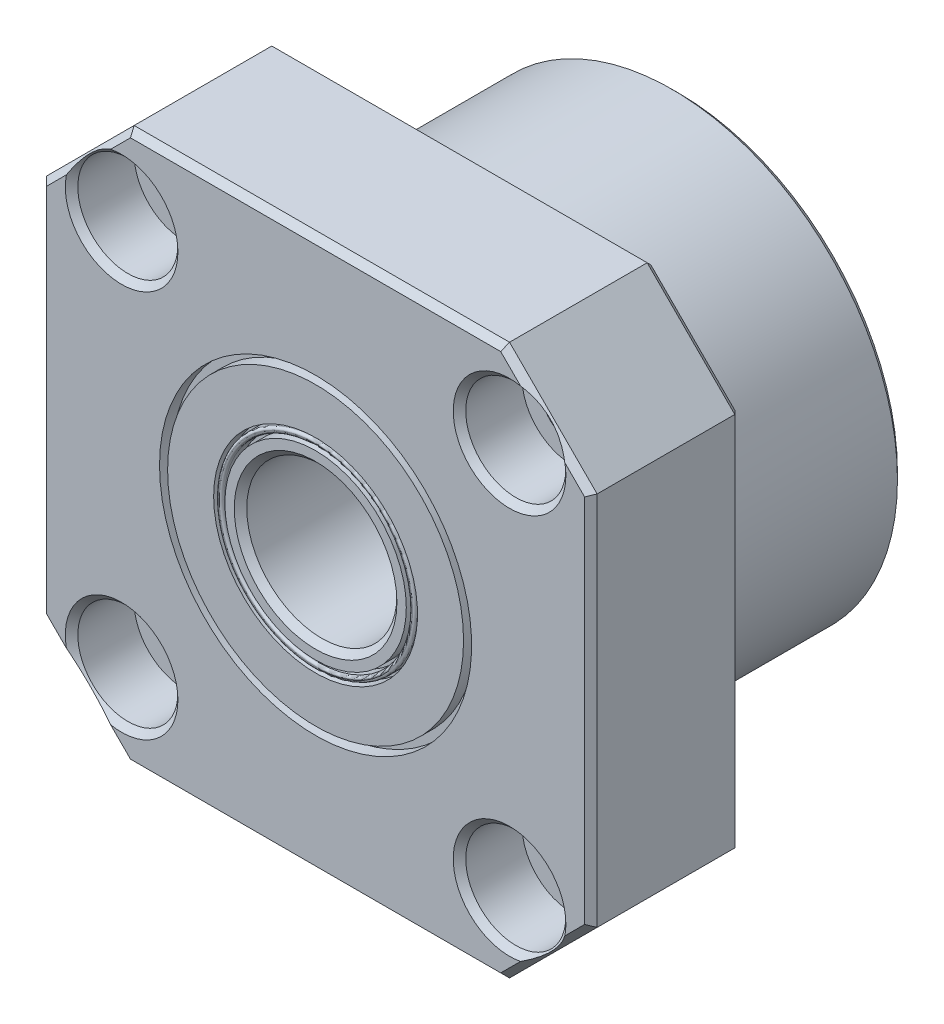
SolidWorks part; units mm, degrees
ref_plane "Plano frontal" through (0, 0, 0) normal (0, 0, 1) x (1, 0, 0)
ref_plane "Plano superior" through (0, 0, 0) normal (0, 1, 0) x (1, 0, 0)
ref_plane "Plano direito" through (0, 0, 0) normal (1, 0, 0) x (0, 0, -1)
sketch "Esboço1" plane through (0, 0, 0) normal (0, 0, 1) x (1, 0, 0)
  line L0 (0, 47.516) -> (0, -52.6832) construction
  line L1 (90.8564, 0) -> (-91.569, 0) construction
  line L3 (-22, 22) -> (22, 22)
  line L4 (-22, 22) -> (-22, -22)
  line L5 (-22, -22) -> (22, -22)
  line L6 (22, 22) -> (22, -22)
  point P9 (22, 0)
  point P10 (0, 22)
  dimension "D1" = 44
  dimension "D2" = 44
extrude "Ressalto-extrusão1" add sketch "Esboço1" along normal blind 12
sketch "Esboço2" plane through (0, 0, 0) normal (0, 0, -1) x (-1, 0, 0)
  line L0 (0, 33.6256) -> (0, -34.0961) construction
  line L1 (39.4463, 0) -> (-45.621, 0) construction
  circle A0 centre (0, 0) radius 18
  dimension "D1" = 36
extrude "Ressalto-extrusão2" add sketch "Esboço2" along normal blind 17
chamfer "Chanfro1" distance 7 angle 45 4 edges at (-22, -22, 6) (22, -22, 6) (22, 22, 6) (-22, 22, 6)
sketch "Esboço3" plane through (0, 0, 12) normal (0, 0, 1) x (1, 0, 0)
  line L0 (0, 30.9393) -> (0, -34.1727) construction
  line L1 (33.4446, 0) -> (-32.6784, 0) construction
  line L2 (-18.5, 18.5) -> (18.5, -18.5) construction
  line L3 (-15, 22) -> (-22, 15) construction
  line L4 (15, -22) -> (22, -15) construction
  line L5 (18.5, 18.5) -> (-18.5, -18.5) construction
  line L6 (22, 15) -> (15, 22) construction
  line L7 (-22, -15) -> (-15, -22) construction
  circle A0 centre (0, 0) radius 6
  circle A1 centre (-15.5, 15.5) radius 2.5
  circle A2 centre (15.5, 15.5) radius 2.5
  circle A3 centre (15.5, -15.5) radius 2.5
  circle A4 centre (-15.5, -15.5) radius 2.5
  dimension "D1" = 5
  dimension "D3" = 12
  dimension "D2" = 31
extrude "Corte-extrusão1" cut sketch "Esboço3" against normal through all and the other way blind 1
sketch "Esboço4" plane through (0, 0, 12) normal (0, 0, 1) x (1, 0, 0)
  line L0 (-15.0272, -21.6297) -> (-22.0083, -14.6486) construction
  line L1 (21.6297, 15.0272) -> (14.6486, 22.0083) construction
  line L2 (22, 15) -> (15, 22) construction
  line L3 (-22, -15) -> (-15, -22) construction
  circle A0 centre (-15.5, 15.5) radius 4
  circle A1 centre (15.5, 15.5) radius 4
  circle A2 centre (15.5, -15.5) radius 4
  circle A3 centre (-15.5, -15.5) radius 4
  dimension "D1" = 8
  dimension "D2" = 8
  dimension "D3" = 8
  dimension "D4" = 8
extrude "Corte-extrusão2" cut sketch "Esboço4" against normal blind 5
chamfer "Chanfro2" distance 0.5 angle 45 15 edges at (-18, 0, -17) (6, 0, -17) (0, 22, 12) (22, 0, 12) (0, -22, 12) (-22, 0, 12) (6, 0, 12) (-11.5, 15.5, 12) (19.5, 15.5, 12) (19.5, -15.5, 12) (-11.5, -15.5, 12) (-18.5, 18.5, 12) (18.5, 18.5, 12) (18.5, -18.5, 12) (-18.5, -18.5, 12)
chamfer "Chanfro3" distance 0.5 angle 45 8 edges at (18.5, -18.5, 0) (0, -22, 0) (-18.5, -18.5, 0) (-22, 0, 0) (-18.5, 18.5, 0) (22, 0, 0) (18.5, 18.5, 0) (0, 22, 0)
sketch "Esboço5" plane through (0, 0, -17) normal (0, 0, -1) x (-1, 0, 0)
  circle A0 centre (0, 0) radius 7.25
  circle A1 centre (0, 0) radius 7.5
  dimension "D1" = 14.5
  dimension "D2" = 0.25
extrude "Corte-extrusão3" cut sketch "Esboço5" against normal blind 1
sketch "Esboço6" plane through (0, 0, -17) normal (0, 0, -1) x (-1, 0, 0)
  circle A0 centre (0, 0) radius 7.9524
  circle A1 centre (0, 0) radius 8.1467
extrude "Corte-extrusão4" cut sketch "Esboço6" against normal blind 1
sketch "Esboço7" plane through (0, 0, -17) normal (0, 0, -1) x (-1, 0, 0)
  circle A0 centre (0, 0) radius 11.8256
  circle A1 centre (0, 0) radius 12.4704
extrude "Corte-extrusão5" cut sketch "Esboço7" against normal blind 1
fillet "Filete1" radius 0.2 2 edges at (-7.5, 0, -17) (-7.9524, 0, -17)
ref_plane "Plano1" through (0, 0, -2.5) normal (0, 0, 1) x (1, 0, 0)
mirror "Espelhar3" about plane through (0, 0, -2.5) normal (0, 0, 1) of "Corte-extrusão5", "Corte-extrusão4", "Corte-extrusão3"
fillet "Filete2" radius 0.2 2 edges at (-7.5, 0, 12) (-7.9524, 0, 12)
